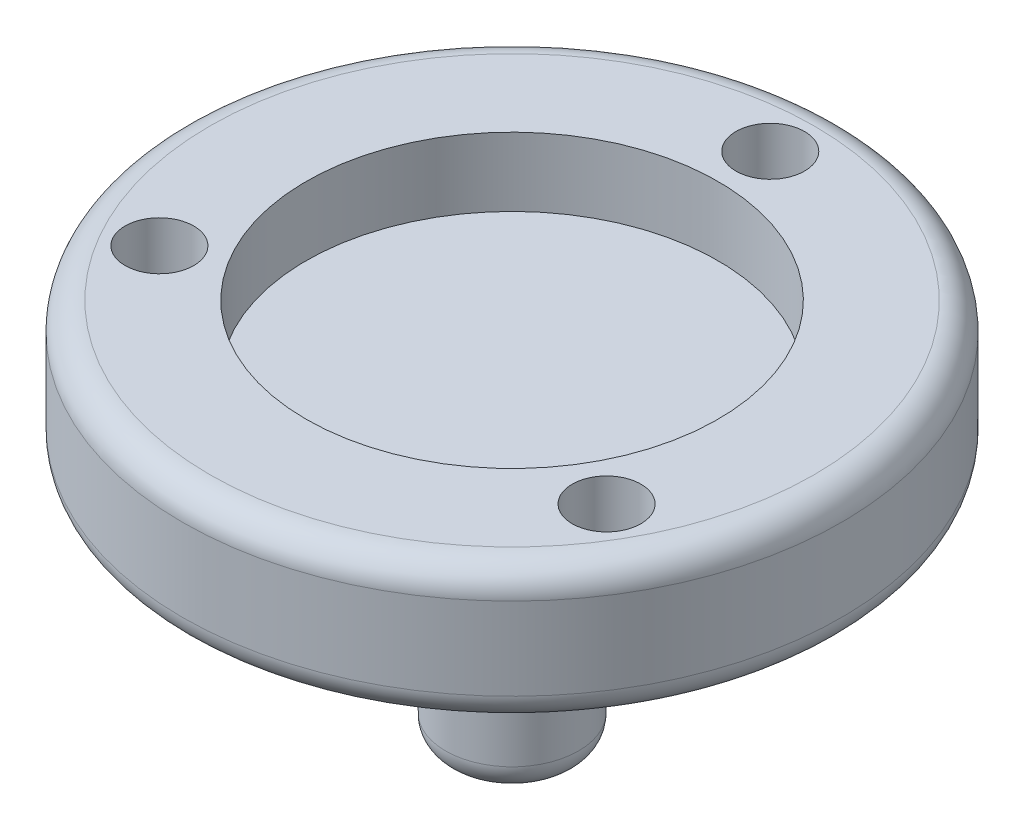
SolidWorks part; units mm, degrees
ref_plane "Front Plane" through (0, 0, 0) normal (0, 0, 1) x (1, 0, 0)
ref_plane "Top Plane" through (0, 0, 0) normal (0, 1, 0) x (1, 0, 0)
ref_plane "Right Plane" through (0, 0, 0) normal (1, 0, 0) x (0, 0, -1)
sketch "Sketch1" plane through (0, 0, 0) normal (0, 1, 0) x (1, 0, 0)
  circle A0 centre (0, 0) radius 15.24
extrude "Boss-Extrude1" add sketch "Sketch1" along normal blind 6.35
sketch "Sketch2" plane through (0, 6.35, 0) normal (0, 1, 0) x (1, 0, 0)
  circle A0 centre (0, 0) radius 9.525
extrude "Cut-Extrude1" cut sketch "Sketch2" against normal blind 3.175
sketch "Sketch3" plane through (0, 0, 0) normal (0, -1, 0) x (1, 0, 0)
  circle A0 centre (0, 0) radius 3.0734
fillet "Fillet4" radius 1.27 1 edges at (0, 6.35, 15.24)
extrude "Boss-Extrude3" add sketch "Sketch3" along normal blind 11.43 contours A0
fillet "Fillet5" radius 1.27 3 edges at (0, -11.43, -3.0734) (0, 0, 15.24) (0, 0, -3.0734)
sketch "Sketch4" plane through (0, 6.35, 0) normal (0, 1, 0) x (1, 0, 0)
  line L0 (0, 0) -> (0, 13.97) construction
  circle A0 centre (0, 0) radius 13.97 construction
  circle A1 centre (0, 0) radius 11.938 construction
  circle A2 centre (0, 11.938) radius 1.5875
extrude "Cut-Extrude2" cut sketch "Sketch4" against normal blind 2.54
ref_axis "Axis1" through (0, 3.175, 0) along (0, 1, 0)
pattern_circular "CirPattern1" count 3 every 120 about axis through (0, 3.175, 0) along (0, 1, 0) of "Cut-Extrude2"
